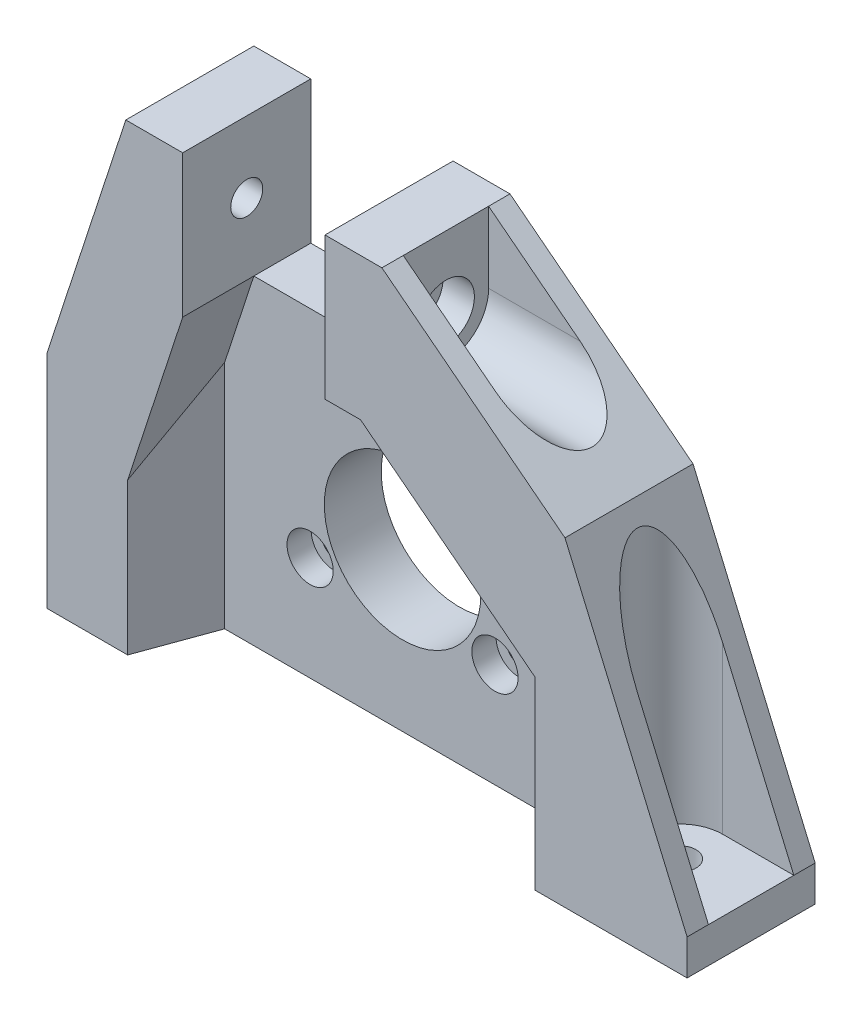
SolidWorks part; units mm, degrees
material "ABS"
ref_plane "Front Plane" through (0, 0, 0) normal (0, 0, 1) x (1, 0, 0)
ref_plane "Top Plane" through (0, 0, 0) normal (0, 1, 0) x (1, 0, 0)
ref_plane "Right Plane" through (0, 0, 0) normal (1, 0, 0) x (0, 0, -1)
sketch "Sketch1" plane through (0, 0, 0) normal (0, 0, 1) x (1, 0, 0)
  line L0 (39.1, 65) -> (39.1, 45)
  line L1 (39.1, 45) -> (19.1, 45)
  line L2 (19.1, 45) -> (19.1, 65)
  line L3 (19.1, 65) -> (11.1, 65)
  line L4 (11.1, 65) -> (0, 31)
  line L5 (0, 31) -> (0, 0)
  line L6 (0, 0) -> (90, 0)
  line L7 (90, 0) -> (90, 5)
  line L8 (90, 5) -> (72.831, 45)
  line L9 (72.831, 45) -> (47.1, 65)
  line L10 (47.1, 65) -> (39.1, 65)
  circle A0 centre (40, 22.15) radius 11
  dimension "D11" = 22
  dimension "D1" = 20
  dimension "D2" = 20
  dimension "D3" = 65
  dimension "D4" = 8
  dimension "D5" = 5
  dimension "D6" = 31
  dimension "D7" = 8
  dimension "D8" = 0.9
  dimension "D9" = 40
  dimension "D10" = 22.15
  dimension "D12" = 40
  dimension "D13" = 90
extrude "Boss-Extrude1" add sketch "Sketch1" along normal blind 18
sketch "Sketch5" plane through (0, 65, 0) normal (0, 1, 0) x (1, 0, 0)
  line L0 (90, -9) -> (80, -9) construction
  line L1 (90, -18) -> (90, 0) construction
  line L2 (90, -15) -> (80, -15)
  line L3 (90, -3) -> (80, -3)
  arc A0 (90, -15) -> (90, -3) centre (90, -9) ccw
  arc A1 (80, -3) -> (80, -15) centre (80, -9) ccw
  point P4 (85, -9)
  dimension "D2" = 6
  dimension "D1" = 10
extrude "Cut-Extrude4" cut sketch "Sketch5" against normal blind 60
sketch "Sketch6" plane through (0, 0, 18) normal (0, 0, 1) x (1, 0, 0)
  line L0 (19.1, 45) -> (15, 32.4414)
  line L1 (15, 32.4414) -> (15, 0)
  line L2 (0, 0) -> (90, 0) construction
  line L3 (15, 0) -> (65, 0)
  line L4 (65, 0) -> (65, 28.755)
  line L5 (19.1, 45) -> (44.1, 45)
  line L6 (11.1, 65) -> (0, 31) construction
  line L7 (44.1, 45) -> (65, 28.755)
  line L8 (72.831, 45) -> (47.1, 65) construction
  line L9 (0, 31) -> (0, 0) construction
  dimension "D1" = 50
  dimension "D2" = 15
  dimension "D3" = 25
extrude "Cut-Extrude5" cut sketch "Sketch6" against normal blind 10
chamfer "Chamfer1" distance 10 angle 20 2 edges at (15, 16.2207, 18) (65, 14.3775, 18) first distance on face at (15, 16.2207, 13) first distance on face at (65, 14.3775, 13)
sketch "Sketch7" plane through (90, 0, 0) normal (1, 0, 0) x (0, 0, -1)
  line L0 (-9, 65) -> (-9, 55) construction
  line L1 (-18, 65) -> (0, 65) construction
  line L2 (-3, 65) -> (-3, 55)
  line L3 (-15, 65) -> (-15, 55)
  arc A0 (-3, 65) -> (-15, 65) centre (-9, 65) ccw
  arc A1 (-15, 55) -> (-3, 55) centre (-9, 55) ccw
  point P4 (-9, 60)
  dimension "D2" = 6
  dimension "D1" = 10
extrude "Cut-Extrude6" cut sketch "Sketch7" against normal blind 42.9
sketch "Sketch8" plane through (0, 0, 0) normal (-1, 0, 0) x (0, 0, 1)
  line L0 (9, 65) -> (9, 55) construction
  line L1 (18, 65) -> (0, 65) construction
  line L2 (15, 65) -> (15, 55)
  line L3 (3, 65) -> (3, 55)
  arc A0 (15, 65) -> (3, 65) centre (9, 65) ccw
  arc A1 (3, 55) -> (15, 55) centre (9, 55) ccw
  point P4 (9, 60)
  dimension "D2" = 6
  dimension "D1" = 10
extrude "Cut-Extrude7" cut sketch "Sketch8" against normal blind 11.1
hole_wizard "CBORE for M3 Hex Socket Head Cap Screw2" positions "Sketch9" profile "Sketch10" counterbore size "M3" standard "DIN"
sketch "Sketch9" plane through (0, 0, 8) normal (0, 0, 1) x (1, 0, 0)
  line L0 (40, 22.15) -> (40, 37.15) construction
  point P0 (40, 37.15)
  point P14 (52.9904, 14.65)
  point P15 (27.0096, 14.65)
  dimension "D1" = 15
  dimension "D2" = 3
sketch "Sketch10" plane through (40, 37.15, 8) normal (1, 0, 0) x (0, -1, 0)
  line L0 (0, 0) -> (0, 9.0215)
  line L1 (0, 9.0215) -> (1.7, 8)
  line L2 (1.7, 8) -> (1.7, 3.4)
  line L3 (1.7, 3.4) -> (3.25, 3.4)
  line L4 (3.25, 3.4) -> (3.25, 0)
  line L5 (3.25, 0) -> (0, 0)
  line L10 (0, 9.0215) -> (-1.7, 8) construction
  line L11 (0, -6.35) -> (0, 107.95) construction
  dimension "Hole Dia." = 3.4
  dimension "Hole Depth" = 8
  dimension "C'Bore Dia." = 6.5
  dimension "C'Bore Depth" = 3.4
  dimension "Drill Angle" = 118
hole_wizard "CBORE for M4 Hex Socket Head Cap Screw1" positions "Sketch11" profile "Sketch12" counterbore size "M4" standard "DIN"
sketch "Sketch11" plane through (47.1, 0, 0) normal (1, 0, 0) x (0, 0, -1)
  point P0 (-9, 55)
sketch "Sketch12" plane through (47.1, 55, 9) normal (0, 1, 0) x (0, 0, -1)
  line L0 (0, 0) -> (0, 9.3519)
  line L1 (0, 9.3519) -> (2.25, 8)
  line L2 (2.25, 8) -> (2.25, 4.4)
  line L3 (2.25, 4.4) -> (4, 4.4)
  line L4 (4, 4.4) -> (4, 0)
  line L5 (4, 0) -> (0, 0)
  line L10 (0, 9.3519) -> (-2.25, 8) construction
  line L11 (0, -6.35) -> (0, 107.95) construction
  dimension "Hole Dia." = 4.5
  dimension "Hole Depth" = 8
  dimension "C'Bore Dia." = 8
  dimension "C'Bore Depth" = 4.4
  dimension "Drill Angle" = 118
hole_wizard "CBORE for M4 Hex Socket Head Cap Screw2" positions "Sketch13" profile "Sketch14" counterbore size "M4" standard "DIN"
sketch "Sketch13" plane through (11.1, 0, 0) normal (-1, 0, 0) x (0, 0, 1)
  point P0 (9, 55)
sketch "Sketch14" plane through (11.1, 55, 9) normal (0, 1, 0) x (0, 0, 1)
  line L0 (0, 0) -> (0, 9.3519)
  line L1 (0, 9.3519) -> (2.25, 8)
  line L2 (2.25, 8) -> (2.25, 4.4)
  line L3 (2.25, 4.4) -> (4, 4.4)
  line L4 (4, 4.4) -> (4, 0)
  line L5 (4, 0) -> (0, 0)
  line L10 (0, 9.3519) -> (-2.25, 8) construction
  line L11 (0, -6.35) -> (0, 107.95) construction
  dimension "Hole Dia." = 4.5
  dimension "Hole Depth" = 8
  dimension "C'Bore Dia." = 8
  dimension "C'Bore Depth" = 4.4
  dimension "Drill Angle" = 118
hole_wizard "M4 Clearance Hole1" positions "Sketch15" profile "Sketch16" hole size "M4" standard "DIN"
sketch "Sketch15" plane through (0, 5, 0) normal (0, 1, 0) x (1, 0, 0)
  point P0 (80, -9)
sketch "Sketch16" plane through (80, 5, 9) normal (1, 0, 0) x (0, 0, 1)
  line L0 (0, 0) -> (0, 9.3519)
  line L1 (0, 9.3519) -> (2.25, 8)
  line L2 (2.25, 8) -> (2.25, 0)
  line L5 (2.25, 0) -> (0, 0)
  line L10 (0, 9.3519) -> (-2.25, 8) construction
  line L11 (0, -6.35) -> (0, 107.95) construction
  dimension "Hole Dia." = 4.5
  dimension "Hole Depth" = 8
  dimension "Drill Angle" = 118
hole_wizard "Ø4.0mm Dowel Hole1" positions "Sketch17" profile "Sketch18" hole size "Ø4.0" standard "DIN"
sketch "Sketch17" plane through (0, 0, 0) normal (0, -1, 0) x (-1, 0, 0)
  line L1 (0, -18) -> (-11.3603, -18) construction
  line L2 (0, 0) -> (-90, 0) construction
  line L3 (0, -18) -> (0, 0) construction
  point P0 (-7, -12)
  point P2 (-7, -6)
  dimension "D1" = 6
  dimension "D2" = 6
  dimension "D3" = 7
sketch "Sketch18" plane through (7, 0, 12) normal (1, 0, 0) x (0, 0, -1)
  line L0 (0, 0) -> (0, 9.2017)
  line L1 (0, 9.2017) -> (2, 8)
  line L2 (2, 8) -> (2, 0)
  line L5 (2, 0) -> (0, 0)
  line L10 (0, 9.2017) -> (-2, 8) construction
  line L11 (0, -6.35) -> (0, 107.95) construction
  dimension "Hole Dia." = 4
  dimension "Hole Depth" = 8
  dimension "Drill Angle" = 118
